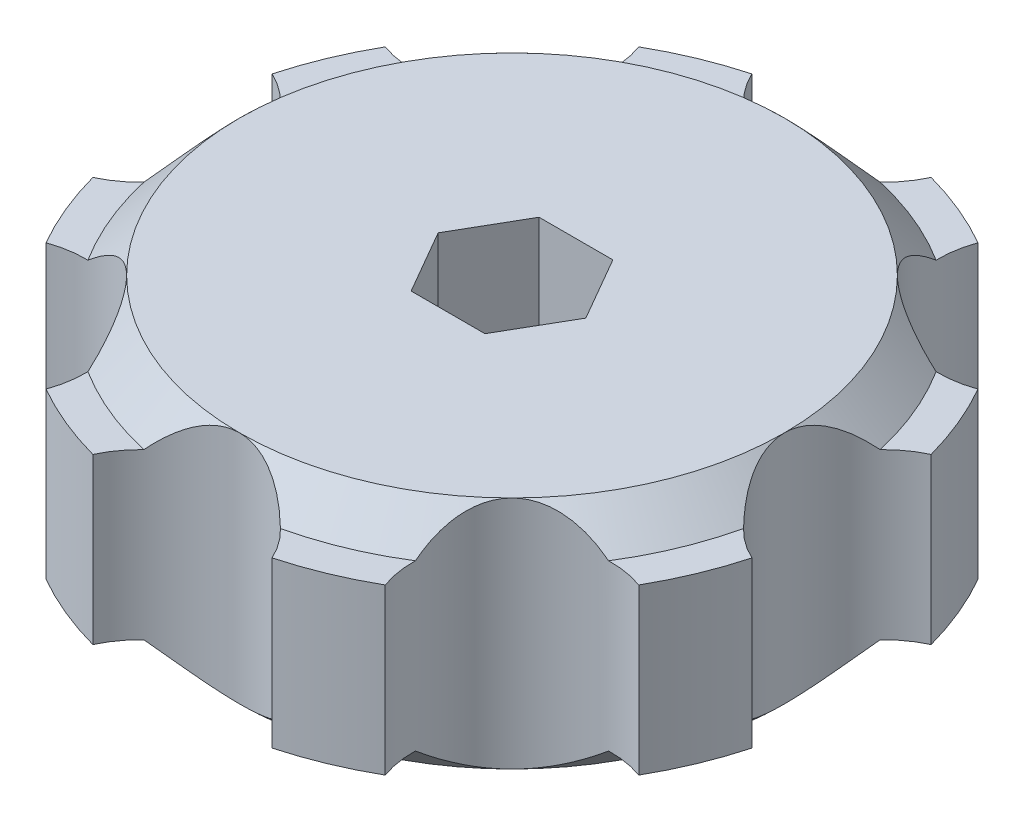
SolidWorks part; units mm, degrees
ref_plane "Front Plane" through (0, 0, 0) normal (0, 0, 1) x (1, 0, 0)
ref_plane "Top Plane" through (0, 0, 0) normal (0, 1, 0) x (1, 0, 0)
ref_plane "Right Plane" through (0, 0, 0) normal (1, 0, 0) x (0, 0, -1)
sketch "Sketch1" plane through (0, 0, 0) normal (0, 1, 0) x (1, 0, 0)
  line L0 (0, -21.2055) -> (21.2055, -21.2055) construction
  line L1 (0, -21.2055) -> (14.9946, -14.9946) construction
  line L2 (14.9946, -14.9946) -> (21.2055, 0) construction
  line L3 (21.2055, 0) -> (14.9946, 14.9946) construction
  line L4 (14.9946, 14.9946) -> (0, 21.2055) construction
  line L5 (0, 21.2055) -> (-14.9946, 14.9946) construction
  line L6 (-14.9946, 14.9946) -> (-21.2055, 0) construction
  line L7 (-21.2055, 0) -> (-14.9946, -14.9946) construction
  line L8 (-14.9946, -14.9946) -> (0, -21.2055) construction
  line L9 (21.2055, -21.2055) -> (21.2055, 0) construction
  arc A1 (5.1161, -18.8079) -> (-5.1161, -18.8079) centre (0, -21.2055) ccw
  arc A2 (-9.6816, -16.9168) -> (-16.9168, -9.6816) centre (-14.9946, -14.9946) ccw
  arc A3 (-18.8079, -5.1161) -> (-18.8079, 5.1161) centre (-21.2055, 0) ccw
  arc A4 (-16.9168, 9.6816) -> (-9.6816, 16.9168) centre (-14.9946, 14.9946) ccw
  arc A5 (-5.1161, 18.8079) -> (5.1161, 18.8079) centre (0, 21.2055) ccw
  arc A6 (9.6816, 16.9168) -> (16.9168, 9.6816) centre (14.9946, 14.9946) ccw
  arc A7 (-9.6816, -16.9168) -> (-5.1161, -18.8079) centre (0, 0) ccw
  arc A8 (-16.9168, -9.6816) -> (-18.8079, -5.1161) centre (0, 0) cw
  arc A9 (-18.8079, 5.1161) -> (-16.9168, 9.6816) centre (0, 0) cw
  arc A10 (-9.6816, 16.9168) -> (-5.1161, 18.8079) centre (0, 0) cw
  arc A11 (5.1161, 18.8079) -> (9.6816, 16.9168) centre (0, 0) cw
  arc A13 (18.8079, 5.1161) -> (18.8079, -5.1161) centre (21.2055, 0) ccw
  arc A14 (16.9168, -9.6816) -> (9.6816, -16.9168) centre (14.9946, -14.9946) ccw
  arc A15 (5.1161, -18.8079) -> (9.6816, -16.9168) centre (0, 0) ccw
  arc A16 (16.9168, -9.6816) -> (18.8079, -5.1161) centre (0, 0) ccw
  arc A17 (18.8079, 5.1161) -> (16.9168, 9.6816) centre (0, 0) ccw
  circle A18 centre (0, 0) radius 19.5913 construction
  circle A19 centre (0, 0) radius 15.5555
  point P23 (0, 0)
  point P27 (-5.1161, -18.8079)
  point P29 (-5.1161, -18.8079)
  point P31 (-7.459, -18.0077)
  point P33 (-7.4973, -18.1)
  point P37 (-9.6816, -16.9168)
  dimension "D1" = 16.23
  dimension "D2" = 0.1
  dimension "D3" = 5.65
  dimension "D4" = 8
extrude "Boss-Extrude1" add sketch "Sketch1" along normal blind 9.4 contours A19 A3 A8 A2 | A19 A2 A7 A1 | A19 A1 A15 A14 | A19 | A19 A14 A16 A13 | A19 A13 A17 A6 | A19 A6 A11 A5 | A19 A5 A10 A4 | A19 A4 A9 A3 region at (6.5615, 0, 15.8409) region at (-6.5615, 0, 15.8409) region at (0, 0, 0) region at (-15.8409, 0, 6.5615) region at (15.8409, 0, 6.5615) region at (-15.8409, 0, -6.5615) region at (15.8409, 0, -6.5615) region at (-6.5615, 0, -15.8409) region at (6.5615, 0, -15.8409)
extrude "Boss-Extrude2" add sketch "Sketch1<4>" along normal blind 2 from surface contours A19 region at (0, 0, 0) starting at face at (0, 9.4, 0)
sketch "Sketch1<4>" plane through (0, 0, 0) normal (0, 1, 0) x (1, 0, 0) same geometry as "Sketch1"
extrude "Boss-Extrude3" add sketch "Sketch1<5>" against normal blind 2 from surface contours A19 region at (0, 0, 0) starting at face at (0, 0, 0)
sketch "Sketch1<5>" plane through (0, 0, 0) normal (0, 1, 0) x (1, 0, 0) same geometry as "Sketch1"
chamfer "Chamfer2" distance 2 angle 45 2 edges at (-14.3714, 9.4, 5.9528) (-14.3714, 0, 5.9528)
chamfer "Chamfer1" [suppressed] distance 1 angle 45
sketch "Sketch2" plane through (0, 11.4, 0) normal (0, 1, 0) x (1, 0, 0)
  line L1 (-2.1073, -3.65) -> (2.1073, -3.65)
  line L2 (2.1073, -3.65) -> (4.2147, 0)
  line L3 (4.2147, 0) -> (2.1073, 3.65)
  line L4 (2.1073, 3.65) -> (-2.1073, 3.65)
  line L5 (-2.1073, 3.65) -> (-4.2147, 0)
  line L6 (-4.2147, 0) -> (-2.1073, -3.65)
  circle A0 centre (0, 0) radius 3.65 construction
  dimension "D1" = 7.3
extrude "Cut-Extrude1" cut sketch "Sketch2" against normal through all
